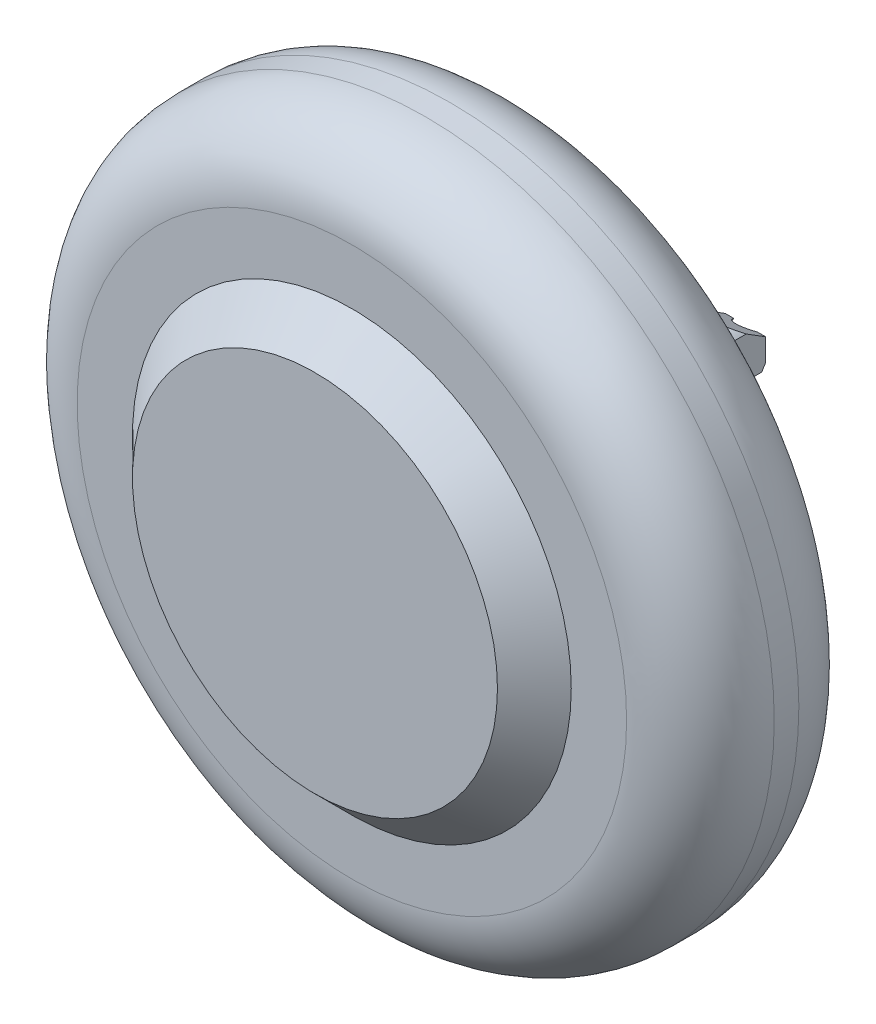
SolidWorks part; units mm, degrees
ref_plane "前视基准面" through (0, 0, 0) normal (0, 0, 1) x (1, 0, 0)
ref_plane "上视基准面" through (0, 0, 0) normal (0, 1, 0) x (1, 0, 0)
ref_plane "右视基准面" through (0, 0, 0) normal (1, 0, 0) x (0, 0, -1)
sketch "草图1" plane through (0, 0, 0) normal (0, 0, 1) x (1, 0, 0)
  circle A0 centre (0, 0) radius 85
  dimension "D1" = 170
extrude "凸台-拉伸1" add sketch "草图1" along normal mid plane 42
sketch "草图2" plane through (0, 0, 0) normal (0, 0, 1) x (1, 0, 0)
  circle A0 centre (0, 0) radius 54.5
  dimension "D1" = 109
extrude "凸台-拉伸2" add sketch "草图2" along normal mid plane 60
chamfer "倒角1" distance 10 angle 45 2 edges at (54.5, 0, -30) (54.5, 0, 30)
sketch "草图3" plane through (0, 0, -30) normal (0, 0, -1) x (-1, 0, 0)
  circle A0 centre (0, 0) radius 7
  dimension "D1" = 14
extrude "凸台-拉伸3" add sketch "草图3" along normal blind 45
cosmetic thread "装饰螺纹线1" parameters "D1"=40, "D2"=11.835
sketch "草图5" plane through (0, 0, -75) normal (0, 0, -1) x (-1, 0, 0)
  line L1 (4.925, -7) -> (-4.925, -7)
  line L2 (4.925, -7) -> (4.925, 7)
  line L3 (4.925, 7) -> (-4.925, 7)
  line L4 (-4.925, -7) -> (-4.925, 7)
  line L5 (4.925, -7) -> (-4.925, 7) construction
  line L6 (4.925, 7) -> (-4.925, -7) construction
  circle A0 centre (0, 0) radius 7 construction
  point P0 (0, 0)
  dimension "D1" = 9.85
extrude "切除-拉伸1" cut sketch "草图5" against normal blind 40 flip side to cut
chamfer "倒角3" distance 1 angle 45 2 edges at (0, -7, -75) (0, 7, -75)
sketch "草图7" plane through (0, 0, -75) normal (0, 0, -1) x (-1, 0, 0)
  circle A0 centre (0, 0) radius 3.5
  dimension "D1" = 7
extrude "切除-拉伸2" cut sketch "草图7" against normal blind 45
fillet "圆角1" radius 18 2 edges at (85, 0, -21) (85, 0, 21)
sketch "草图8" plane through (4.925, 0, 0) normal (1, 0, 0) x (0, 0, -1)
  line L0 (75, 2) -> (75, 7)
  line L1 (75, 3.427) -> (75, -3.427) construction
  line L2 (75, 7) -> (67, 7)
  line L3 (67, 7) -> (75, 2)
  line L4 (75, 0) -> (79.3067, 0) construction
  line L5 (74, 7) -> (30, 7) construction
  dimension "D1" = 2
  dimension "D2" = 8
extrude "切除-拉伸3" cut sketch "草图8" against normal up to next
